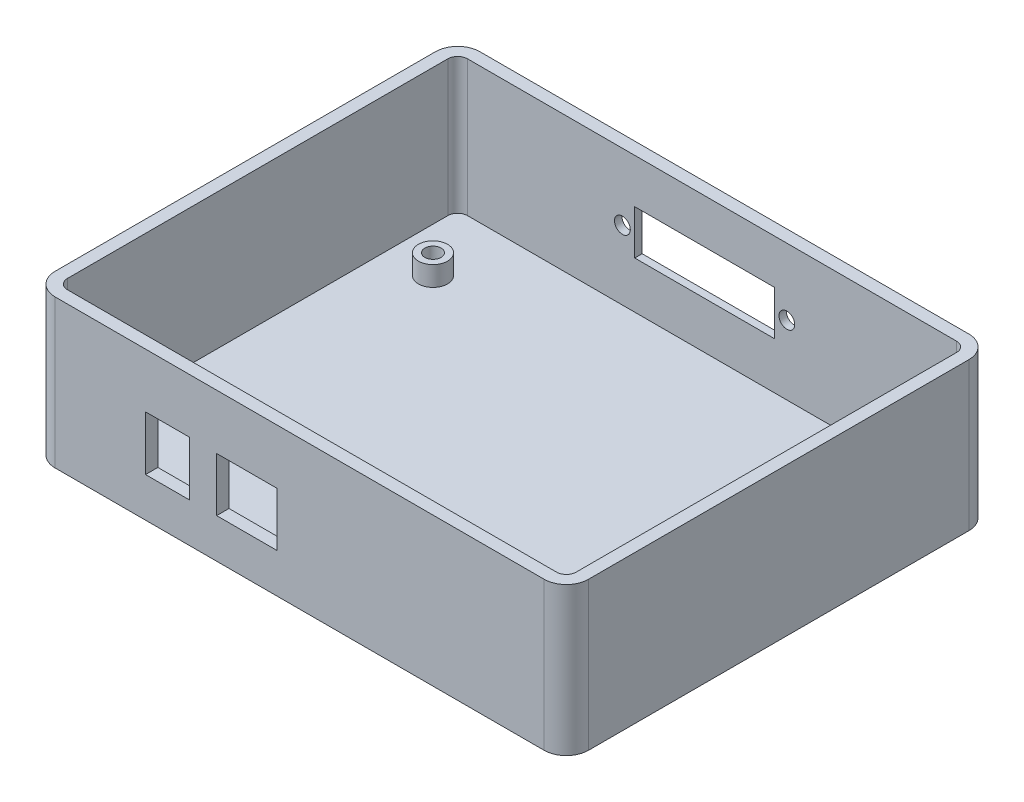
SolidWorks part; units mm, degrees
ref_plane "前视基准面" through (0, 0, 0) normal (0, 0, 1) x (1, 0, 0)
ref_plane "上视基准面" through (0, 0, 0) normal (0, 1, 0) x (1, 0, 0)
ref_plane "右视基准面" through (0, 0, 0) normal (1, 0, 0) x (0, 0, -1)
sketch "草图1" plane through (0, 0, 0) normal (0, 1, 0) x (1, 0, 0)
  line L1 (-45, -35) -> (45, -35) construction
  line L2 (-45, -35) -> (-45, 35) construction
  line L3 (-45, 35) -> (45, 35) construction
  line L4 (45, -35) -> (45, 35) construction
  line L5 (-45, -35) -> (45, 35) construction
  line L6 (-45, 35) -> (45, -35) construction
  line L7 (41, -31) -> (-41, -31) construction
  line L8 (41, -31) -> (41, 31) construction
  line L9 (41, 31) -> (-41, 31) construction
  line L10 (-41, -31) -> (-41, 31) construction
  line L11 (41, -31) -> (-41, 31) construction
  line L12 (41, 31) -> (-41, -31) construction
  line L13 (-50, 45) -> (53, 45)
  line L14 (-50, 45) -> (-50, -36)
  line L15 (-50, -36) -> (53, -36)
  line L16 (53, 45) -> (53, -36)
  circle A0 centre (41, 31) radius 1.65
  circle A1 centre (41, -31) radius 1.65
  circle A2 centre (-41, -31) radius 1.65
  circle A3 centre (-41, 31) radius 1.65
  point P0 (0, 0)
  point P6 (0, 0)
  dimension "D5" = 3.3
  dimension "D1" = 70
  dimension "D2" = 90
  dimension "D3" = 62
  dimension "D4" = 82
  dimension "D6" = 5
  dimension "D7" = 8
  dimension "D8" = 10
  dimension "D9" = 1
extrude "凸台-拉伸1" add sketch "草图1" along normal blind 2.5
fillet "圆角1" radius 2 4 edges at (53, 1.25, 36) (53, 1.25, -45) (-50, 1.25, 36) (-50, 1.25, -45)
sketch "草图4" plane through (0, 0, 0) normal (0, -1, 0) x (1, 0, 0)
  line L0 (51, 38.5) -> (-48, 38.5)
  line L1 (-52.5, 34) -> (-52.5, -43)
  line L2 (-48, -47.5) -> (51, -47.5)
  line L3 (55.5, -43) -> (55.5, 34)
  line L4 (51, 36) -> (-48, 36)
  line L5 (53, -43) -> (53, 34)
  line L6 (-48, -45) -> (51, -45)
  line L7 (-50, 34) -> (-50, -43)
  line L8 (51, 36) -> (-48, 36)
  line L9 (53, -43) -> (53, 34)
  line L10 (-48, -45) -> (51, -45)
  line L11 (-50, 34) -> (-50, -43)
  arc A0 (-48, 38.5) -> (-52.5, 34) centre (-48, 34) ccw
  arc A1 (-52.5, -43) -> (-48, -47.5) centre (-48, -43) ccw
  arc A2 (51, -47.5) -> (55.5, -43) centre (51, -43) ccw
  arc A3 (55.5, 34) -> (51, 38.5) centre (51, 34) ccw
  arc A4 (53, 34) -> (51, 36) centre (51, 34) ccw
  arc A5 (51, -45) -> (53, -43) centre (51, -43) ccw
  arc A6 (-50, -43) -> (-48, -45) centre (-48, -43) ccw
  arc A7 (-48, 36) -> (-50, 34) centre (-48, 34) ccw
  arc A8 (53, 34) -> (51, 36) centre (51, 34) ccw
  arc A9 (51, -45) -> (53, -43) centre (51, -43) ccw
  arc A10 (-50, -43) -> (-48, -45) centre (-48, -43) ccw
  arc A11 (-48, 36) -> (-50, 34) centre (-48, 34) ccw
  dimension "D1" = 0
  dimension "D2" = 2.5
extrude "凸台-拉伸2" add sketch "草图4" against normal blind 30
sketch "草图5" plane through (0, 2.5, 0) normal (0, 1, 0) x (1, 0, 0)
  circle A0 centre (-41, -31) radius 1.65 construction
  circle A1 centre (41, -31) radius 1.65 construction
  circle A2 centre (41, 31) radius 1.65 construction
  circle A3 centre (-41, 31) radius 1.65 construction
  circle A4 centre (-41, -31) radius 1.65
  circle A5 centre (41, -31) radius 1.65
  circle A6 centre (41, 31) radius 1.65
  circle A7 centre (-41, 31) radius 1.65
  circle A8 centre (-41, -31) radius 2.95
  circle A9 centre (41, -31) radius 2.95
  circle A10 centre (41, 31) radius 2.95
  circle A11 centre (-41, 31) radius 2.95
  dimension "D1" = 1.3
extrude "凸台-拉伸3" add sketch "草图5" along normal blind 4
sketch "草图6" plane through (0, 0, 38.5) normal (0, 0, 1) x (1, 0, 0)
  line L0 (-52.5, 30) -> (-52.5, 0) construction
  line L1 (-29.7, 19) -> (-20.8, 19)
  line L2 (-29.7, 19) -> (-29.7, 8)
  line L3 (-29.7, 8) -> (-20.8, 8)
  line L4 (-20.8, 19) -> (-20.8, 8)
  line L5 (-15.3, 18.9) -> (-3.1, 18.9)
  line L6 (-15.3, 18.9) -> (-15.3, 8)
  line L7 (-15.3, 8) -> (-3.1, 8)
  line L8 (-3.1, 18.9) -> (-3.1, 8)
  line L9 (-39.35, 6.5) -> (-42.65, 6.5) construction
  dimension "D1" = 8.9
  dimension "D2" = 12.2
  dimension "D3" = 31.7
  dimension "D4" = 1.5
  dimension "D5" = 49.4
  dimension "D6" = 11
  dimension "D7" = 10.9
extrude "切除-拉伸1" cut sketch "草图6" against normal up to next
sketch "草图7" plane through (0, 0, -47.5) normal (0, 0, -1) x (-1, 0, 0)
  line L0 (-16.65, 16.5) -> (16.65, 16.5) construction
  line L1 (-14.15, 21) -> (14.15, 21)
  line L2 (-14.15, 21) -> (-14.15, 12)
  line L3 (-14.15, 12) -> (14.15, 12)
  line L4 (14.15, 21) -> (14.15, 12)
  line L5 (48, 0) -> (-51, 0) construction
  circle A0 centre (-16.65, 16.5) radius 1.6
  circle A1 centre (16.65, 16.5) radius 1.6
  point P8 (-14.15, 16.5)
  point P9 (0, 16.5)
  point P10 (0, 21)
  dimension "D4" = 3.2
  dimension "D1" = 28.3
  dimension "D2" = 9
  dimension "D3" = 33.3
  dimension "D5" = 12
extrude "切除-拉伸2" cut sketch "草图7" against normal up to next
sketch "草图8" plane through (0, 0, -47.5) normal (0, 0, -1) x (-1, 0, 0)
  line L0 (-14.15, 21) -> (14.15, 21) construction
  line L1 (-19.8, 22.95) -> (19.8, 22.95)
  line L2 (-19.8, 22.95) -> (-19.8, 10.05)
  line L3 (-19.8, 10.05) -> (19.8, 10.05)
  line L4 (19.8, 22.95) -> (19.8, 10.05)
  line L5 (-16.65, 16.5) -> (16.65, 16.5) construction
  point P4 (18.5962, 22.7503)
  point P8 (0, 21)
  point P9 (0, 22.95)
  point P10 (19.8, 16.5)
  dimension "D1" = 12.9
  dimension "D2" = 39.6
extrude "切除-拉伸3" cut sketch "草图8" against normal blind 1
